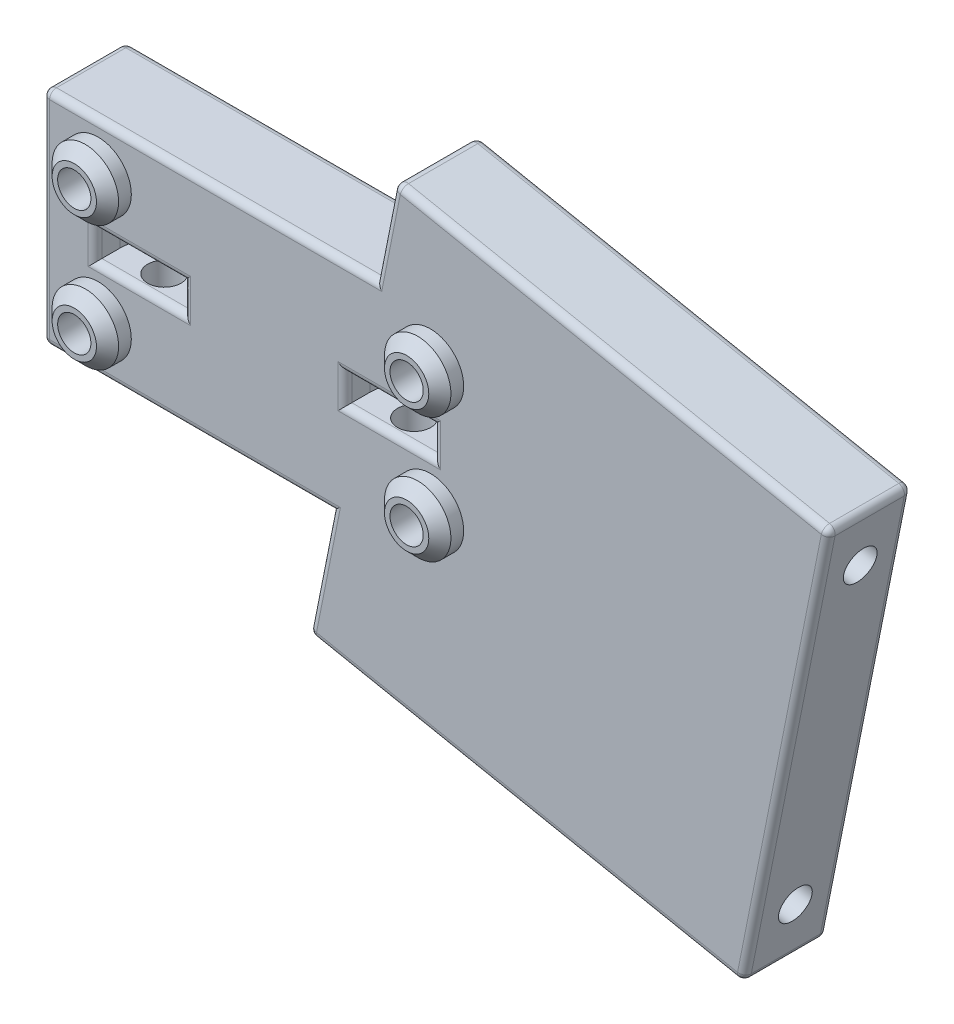
SolidWorks part; units mm, degrees
ref_plane "Front Plane" through (0, 0, 0) normal (0, 0, 1) x (1, 0, 0)
ref_plane "Top Plane" through (0, 0, 0) normal (0, 1, 0) x (1, 0, 0)
ref_plane "Right Plane" through (0, 0, 0) normal (1, 0, 0) x (0, 0, -1)
sketch "Sketch1" plane through (0, 0, 0) normal (0, 0, 1) x (1, 0, 0)
  line L2 (-38.1, -12.7) -> (-38.1, 12.7)
  line L3 (-38.1, 12.7) -> (38.1, 12.7)
  line L10 (38.1, -12.7) -> (38.1, 12.7)
  line L11 (-38.1, -12.7) -> (38.1, -12.7)
  line L14 (-38.1, 12.7) -> (38.1, -12.7) construction
  point P2 (0, 0)
  dimension "D1" = 76.2
  dimension "D2" = 25.4
extrude "Boss-Extrude1" add sketch "Sketch1" along normal blind 9.525
sketch "Sketch6" plane through (0, 0, 9.525) normal (0, 0, -1) x (-1, 0, 0)
  line L4 (7.6422, -26.3067) -> (-42.1817, -36.2172)
  line L6 (7.6422, -26.3067) -> (-2.2683, 23.5172)
  line L23 (-42.1817, -36.2172) -> (-52.0922, 13.6067)
  line L24 (-2.2683, 23.5172) -> (-52.0922, 13.6067)
  line L25 (7.6422, -26.3067) -> (-52.0922, 13.6067) construction
  line L26 (-42.1817, -36.2172) -> (-2.2683, 23.5172) construction
  line L27 (-38.1, 12.7) -> (38.1, 12.7) construction
  point P1 (-22.225, -6.35)
  dimension "D1" = 50.8
  dimension "D2" = 50.8
  dimension "D3" = 11.25
  dimension "D4" = 6.35
  dimension "D5" = 22.225
extrude "Boss-Extrude2" add sketch "Sketch6" along normal up to surface (9.525 mm away) up to face at (0, 0, 0)
sketch "Sketch4" plane through (0, 0, 0) normal (0, 1, 0) x (1, 0, 0)
  line L7 (0.1167, -9.525) -> (-38.1, -9.525) construction
  line L8 (-32.0992, -6.6675) -> (-32.0992, -9.525)
  line L9 (-21.9392, -6.6675) -> (-21.9392, -9.525)
  line L10 (-21.9392, -9.525) -> (-32.0992, -9.525)
  line L11 (-38.1, -9.525) -> (-38.1, 0) construction
  arc A2 (-21.9392, -6.6675) -> (-32.0992, -6.6675) centre (-27.0192, -6.6675) ccw
  dimension "D1" = 10.16
  dimension "D2" = 2.8575
  dimension "D3" = 11.0808
extrude "Cut-Extrude2" cut sketch "Sketch4" against normal mid plane 3.302
ref_plane "Plane3" through (-12.7, 0, 0) normal (-1, 0, 0) x (0, 0, 1)
sketch "Sketch2" plane through (0, 0, 9.525) normal (0, 0, 1) x (1, 0, 0)
  line L1 (-38.1, 12.7) -> (-38.1, -12.7) construction
  line L2 (0, 0) -> (-38.1, 0) construction
  line L3 (-38.1, 12.7) -> (-38.1, -12.7) construction
  circle A0 centre (-31.75, 7.1755) radius 1.905
  circle A1 centre (-31.75, -7.1755) radius 1.905
  dimension "D1" = 3.81
  dimension "D2" = 14.351
  dimension "D3" = 6.35
extrude "Cut-Extrude1" cut sketch "Sketch2" against normal through all both and the other way through all
sketch "Sketch11" plane through (0, 0, 9.525) normal (0, 0, 1) x (1, 0, 0)
  circle A0 centre (-31.75, 7.1755) radius 3.81
  circle A1 centre (-31.75, 7.1755) radius 1.905
  circle A2 centre (-31.75, 7.1755) radius 1.905 construction
  circle A3 centre (-31.75, -7.1755) radius 3.81
  circle A4 centre (-31.75, -7.1755) radius 1.905
  dimension "D1" = 7.62
extrude "Boss-Extrude5" add sketch "Sketch11" along normal blind 2.7305
sketch "Sketch5" plane through (0, 12.7, 0) normal (0, 1, 0) x (1, 0, 0)
  line L0 (0.1167, -9.525) -> (-38.1, -9.525) construction
  line L1 (-38.1, -9.525) -> (-38.1, 0) construction
  circle A0 centre (-27.0192, -6.6675) radius 1.905
  dimension "D3" = 3.81
  dimension "D1" = 2.8575
  dimension "D2" = 11.0808
extrude "Cut-Extrude3" cut sketch "Sketch5" against normal through all from offset 6.35 offset against normal yes
mirror "Mirror1" about plane through (-12.7, 0, 0) normal (-1, 0, 0) of "Cut-Extrude1", "Cut-Extrude3", "Cut-Extrude2", "Boss-Extrude5"
chamfer "Chamfer4" distance 1.27 angle 45 4 edges at (-27.94, -7.1755, 12.2555) (2.54, -7.1755, 12.2555) (2.54, 7.1755, 12.2555) (-27.94, 7.1755, 12.2555)
fillet "Fillet3" radius 0.7937 30 edges at (-38.1, 0, 9.525) (-38.1, -12.7, 4.7625) (-38.1, 0, 0) (-38.1, 12.7, 4.7625) (-18.9917, 12.7, 0) (-18.9917, 12.7, 9.525) (1.1925, 18.1086, 9.525) (1.1925, 18.1086, 0) (2.2683, 23.5172, 4.7625) (27.1803, 18.5619, 0) (27.1803, 18.5619, 9.525) (52.0922, 13.6067, 4.7625) (47.1369, -11.3053, 0) (47.1369, -11.3053, 9.525) (42.1817, -36.2172, 4.7625) (17.2697, -31.2619, 0) (17.2697, -31.2619, 9.525) (-7.6422, -26.3067, 4.7625) (-6.289, -19.5033, 9.525) (-6.289, -19.5033, 0) (-21.5179, -12.7, 0) (-21.5179, -12.7, 9.525) (1.6193, -1.651, 9.525) (6.6993, 0, 9.525) (1.6193, 1.651, 9.525) (-3.4607, 0, 9.525) (-21.9392, 0, 9.525) (-32.0992, 0, 9.525) (-27.0192, 1.651, 9.525) (-27.0192, -1.651, 9.525)
sketch "Sketch12" plane through (47.5061, -9.4495, 0) normal (0.9808, -0.1951, 0) x (0, 0, -1)
  circle A6 centre (-4.7625, -20.9421) radius 1.905
  circle A7 centre (-4.7625, 17.1579) radius 1.905
  dimension "D1" = 3.81
extrude "Cut-Extrude4" cut sketch "Sketch12" against normal blind 9.525
sketch "Sketch13" plane through (-2.3178, 0.461, 0) normal (-0.9808, 0.1951, 0) x (0, 0, 1)
  circle A0 centre (4.7625, 17.1579) radius 1.905
  circle A1 centre (4.7625, -20.9421) radius 1.905
  dimension "D1" = 3.81
extrude "Cut-Extrude5" cut sketch "Sketch13" against normal blind 9.525
